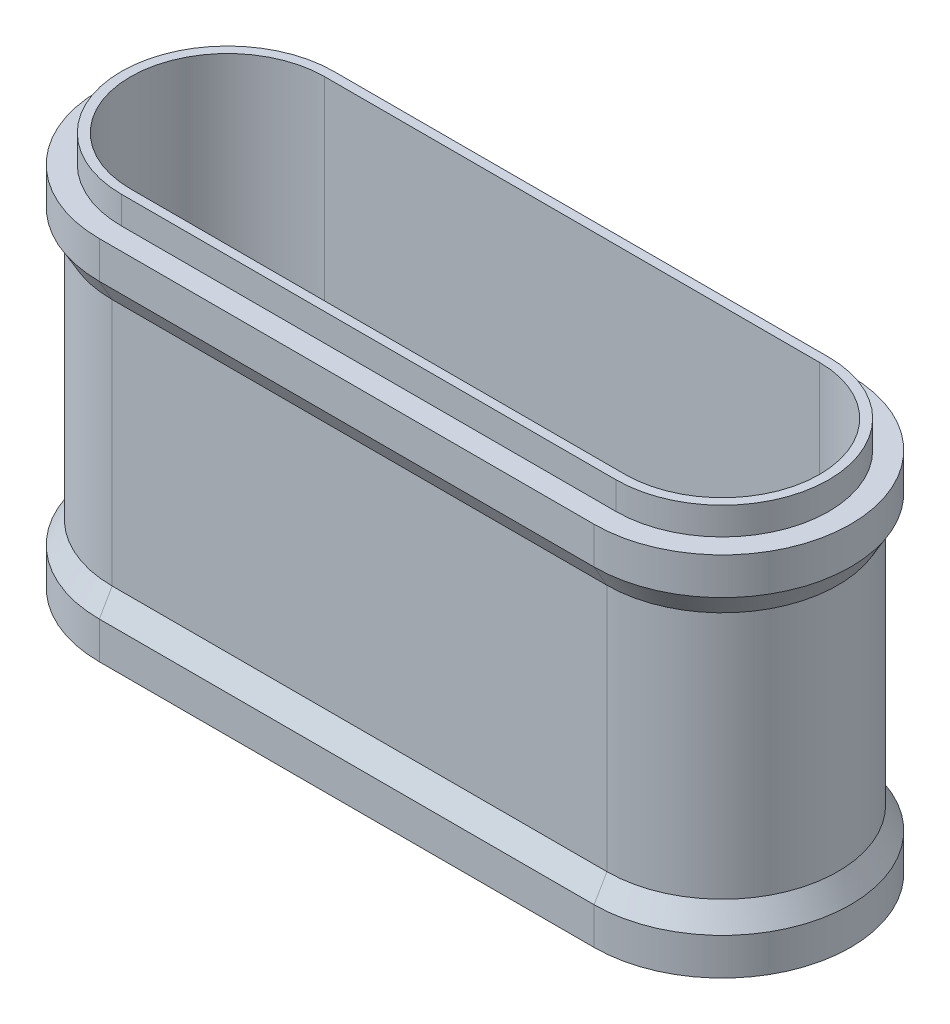
SolidWorks part; units mm, degrees
ref_plane "Front Plane" through (0, 0, 0) normal (0, 0, 1) x (1, 0, 0)
ref_plane "Top Plane" through (0, 0, 0) normal (0, 1, 0) x (1, 0, 0)
ref_plane "Right Plane" through (0, 0, 0) normal (1, 0, 0) x (0, 0, -1)
sketch "Sketch1" plane through (0, 0, 0) normal (0, 1, 0) x (1, 0, 0)
  line L0 (-13.5, 0) -> (13.5, 0) construction
  line L1 (-13.5, 5.3) -> (13.5, 5.3)
  line L2 (-13.5, -5.3) -> (13.5, -5.3)
  line L3 (-13.5, 6.3) -> (13.5, 6.3)
  line L4 (-13.5, -6.3) -> (13.5, -6.3)
  arc A0 (-13.5, 5.3) -> (-13.5, -5.3) centre (-13.5, 0) ccw
  arc A1 (13.5, -5.3) -> (13.5, 5.3) centre (13.5, 0) ccw
  arc A2 (13.5, -6.3) -> (13.5, 6.3) centre (13.5, 0) ccw
  arc A3 (-13.5, 6.3) -> (-13.5, -6.3) centre (-13.5, 0) ccw
  point P2 (0, 0)
  dimension "D1" = 27
  dimension "D2" = 10.6
  dimension "D3" = 1
extrude "Boss-Extrude1" add sketch "Sketch1" along normal blind 10 and the other way blind 10
sketch "Sketch2" plane through (0, 10, 0) normal (0, 1, 0) x (1, 0, 0)
  line L0 (-13.5, -5.3) -> (13.5, -5.3) construction
  line L1 (13.5, 5.3) -> (-13.5, 5.3) construction
  line L2 (-13.5, -5.3) -> (13.5, -5.3)
  line L3 (13.5, 5.3) -> (-13.5, 5.3)
  line L4 (13.5, 0) -> (-13.5, 0) construction
  line L5 (13.5, -7) -> (-13.5, -7)
  line L6 (13.5, 7) -> (-13.5, 7)
  arc A1 (-13.5, 5.3) -> (-13.5, -5.3) centre (-13.5, 0) ccw construction
  arc A2 (13.5, -5.3) -> (13.5, 5.3) centre (13.5, 0) ccw construction
  arc A3 (-13.5, 5.3) -> (-13.5, -5.3) centre (-13.5, 0) ccw
  arc A4 (13.5, -5.3) -> (13.5, 5.3) centre (13.5, 0) ccw
  arc A5 (13.5, -7) -> (13.5, 7) centre (13.5, 0) ccw
  arc A6 (-13.5, 7) -> (-13.5, -7) centre (-13.5, 0) ccw
  point P6 (0, 0)
  dimension "D1" = 14
extrude "Boss-Extrude2" add sketch "Sketch2" against normal blind 1.5
mirror "Mirror1" about plane through (0, 0, 0) normal (0, 1, 0) of "Boss-Extrude2"
sketch "Sketch3" plane through (0, 10, 0) normal (0, 1, 0) x (1, 0, 0)
  line L0 (-13.5, -5.3) -> (13.5, -5.3) construction
  line L1 (13.5, 5.3) -> (-13.5, 5.3) construction
  line L2 (-13.5, -5.3) -> (13.5, -5.3)
  line L3 (13.5, 5.3) -> (-13.5, 5.3)
  line L4 (-13.5, -5.8) -> (13.5, -5.8)
  line L5 (13.5, 5.8) -> (-13.5, 5.8)
  arc A0 (13.5, -5.3) -> (13.5, 5.3) centre (13.5, 0) ccw construction
  arc A1 (-13.5, 5.3) -> (-13.5, -5.3) centre (-13.5, 0) ccw construction
  arc A2 (13.5, -5.3) -> (13.5, 5.3) centre (13.5, 0) ccw
  arc A3 (-13.5, 5.3) -> (-13.5, -5.3) centre (-13.5, 0) ccw
  arc A4 (13.5, -5.8) -> (13.5, 5.8) centre (13.5, 0) ccw
  arc A5 (-13.5, 5.8) -> (-13.5, -5.8) centre (-13.5, 0) ccw
  dimension "D1" = 0.5
extrude "Boss-Extrude3" add sketch "Sketch3" along normal blind 1.5
chamfer "Chamfer1" distance 1 angle 60 8 edges at (19.8, -8.5, 0) (0, -8.5, -6.3) (0, -8.5, 6.3) (-19.8, -8.5, 0) (0, 8.5, -6.3) (19.8, 8.5, 0) (-19.8, 8.5, 0) (0, 8.5, 6.3) first distance on face at (0, -8.5, 0) first distance on face at (0, 8.5, 0)
